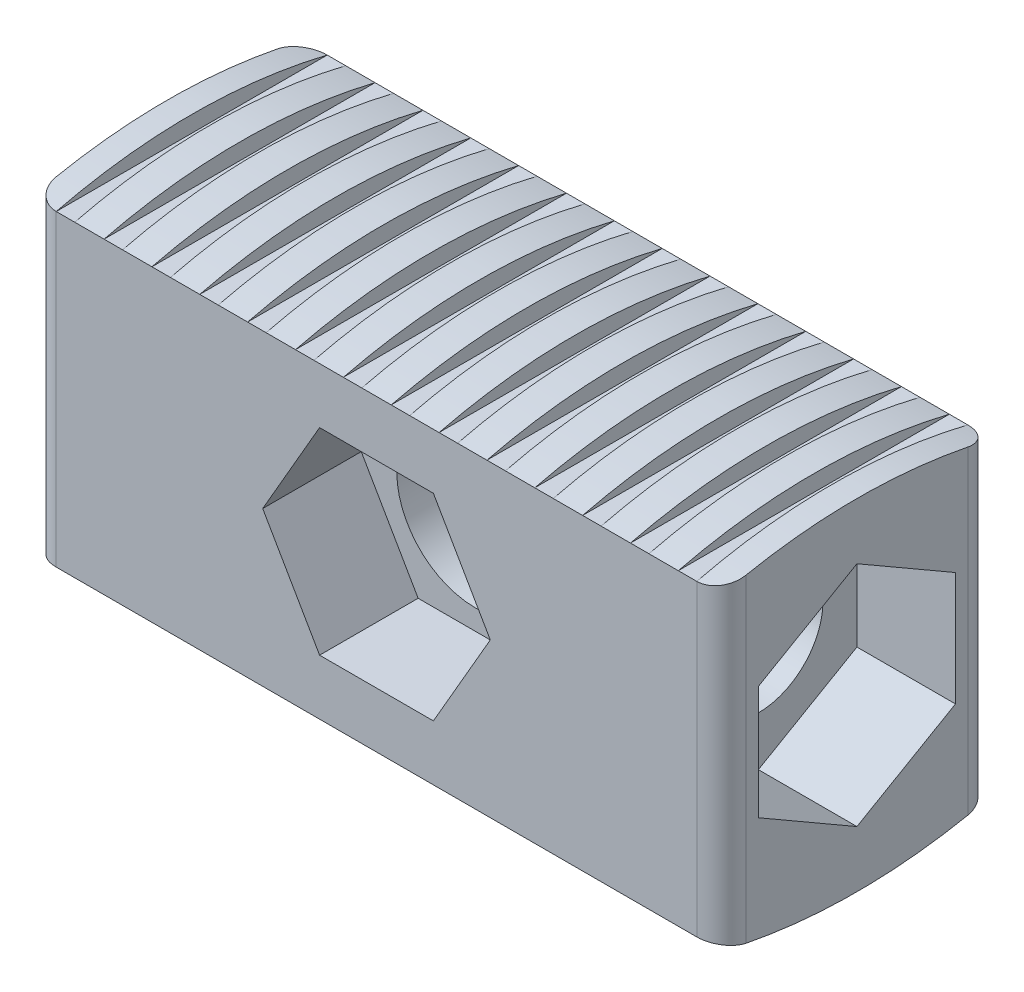
SolidWorks part; units mm, degrees
material "ABS"
ref_plane "Front Plane" through (0, 0, 0) normal (0, 0, 1) x (1, 0, 0)
ref_plane "Top Plane" through (0, 0, 0) normal (0, 1, 0) x (1, 0, 0)
ref_plane "Right Plane" through (0, 0, 0) normal (1, 0, 0) x (0, 0, -1)
sketch "Sketch1" plane through (0, 0, 0) normal (0, 0, 1) x (1, 0, 0)
  line L2 (2.8868, 5) -> (-2.8868, 5) construction
  line L3 (-2.8868, 5) -> (-5.7735, 0) construction
  line L4 (-5.7735, 0) -> (-2.8868, -5) construction
  line L5 (-2.8868, -5) -> (2.8868, -5) construction
  line L18 (0, 5) -> (0, -5) construction
  line L19 (0, 0) -> (0, -7.5) construction
  line L20 (5.7735, 0) -> (2.8868, 5) [skipped]
  line L21 (2.8868, -5) -> (5.7735, 0) [skipped]
  line L22 (-5.7735, 0) -> (-14, 0) construction
  line L23 (0, 5) -> (0, 7.5) construction
  line L24 (14, -7.5) -> (-14, -7.5)
  line L25 (-14, -7.5) -> (-14, 0)
  line L26 (-14, 0) -> (-14, 7.5)
  line L27 (-14, 7.5) -> (14, 7.5)
  line L28 (5.7735, 0) -> (14, 0) construction
  line L29 (14, 0) -> (14, 7.5)
  line L30 (14, -7.5) -> (14, 0)
  line L31 (5.7735, 0) -> (2.8868, -5) construction
  line L32 (2.8868, 5) -> (5.7735, 0) construction
  circle A0 centre (0, 0) radius 5 construction
  circle A2 centre (0, 0) radius 3.175
  dimension "D4" = 6.35
  dimension "D1" = 10
  dimension "D2" = 7.5
  dimension "D3" = 28
extrude "Boss-Extrude1" add sketch "Sketch1" along normal blind 11
sketch "Sketch3" plane through (0, 0, 11) normal (0, 0, 1) x (1, 0, 0)
  line L1 (4.6188, 0) -> (2.3094, 4)
  line L2 (2.3094, 4) -> (-2.3094, 4)
  line L3 (-2.3094, 4) -> (-4.6188, 0)
  line L4 (-4.6188, 0) -> (-2.3094, -4)
  line L5 (-2.3094, -4) -> (2.3094, -4)
  line L6 (2.3094, -4) -> (4.6188, 0)
  circle A0 centre (0, 0) radius 4 construction
  dimension "D1" = 8
extrude "Cut-Extrude3" cut sketch "Sketch3" against normal blind 4
ref_plane "Plane1" through (0, 0, 5.5) normal (0, 0, -1) x (-1, 0, 0)
sketch "Sketch6" plane through (0, -7.5, 0) normal (0, -1, 0) x (1, 0, 0)
  line L0 (-14, 11) -> (14, 11) construction
  line L1 (-13, 0) -> (-12.25, 0)
  line L2 (-13, 0) -> (-13, 11)
  line L3 (-13, 11) -> (-12.25, 11)
  line L4 (-12.25, 0) -> (-12.25, 11)
  line L5 (-14, 11) -> (-14, 0) construction
  line L6 (-11.0577, 0) -> (-11.0577, 11)
  line L7 (-11.0577, 0) -> (-10.3077, 0)
  line L8 (-10.3077, 0) -> (-10.3077, 11)
  line L9 (-11.0577, 11) -> (-10.3077, 11)
  line L10 (-9.1154, 0) -> (-9.1154, 11)
  line L11 (-9.1154, 0) -> (-8.3654, 0)
  line L12 (-8.3654, 0) -> (-8.3654, 11)
  line L13 (-9.1154, 11) -> (-8.3654, 11)
  line L14 (-7.1731, 0) -> (-7.1731, 11)
  line L15 (-7.1731, 0) -> (-6.4231, 0)
  line L16 (-6.4231, 0) -> (-6.4231, 11)
  line L17 (-7.1731, 11) -> (-6.4231, 11)
  line L18 (-5.2308, 0) -> (-5.2308, 11)
  line L19 (-5.2308, 0) -> (-4.4808, 0)
  line L20 (-4.4808, 0) -> (-4.4808, 11)
  line L21 (-5.2308, 11) -> (-4.4808, 11)
  line L22 (-3.2885, 0) -> (-3.2885, 11)
  line L23 (-3.2885, 0) -> (-2.5385, 0)
  line L24 (-2.5385, 0) -> (-2.5385, 11)
  line L25 (-3.2885, 11) -> (-2.5385, 11)
  line L26 (-1.3462, 0) -> (-1.3462, 11)
  line L27 (-1.3462, 0) -> (-0.5962, 0)
  line L28 (-0.5962, 0) -> (-0.5962, 11)
  line L29 (-1.3462, 11) -> (-0.5962, 11)
  line L30 (0.5962, 0) -> (0.5962, 11)
  line L31 (0.5962, 0) -> (1.3462, 0)
  line L32 (1.3462, 0) -> (1.3462, 11)
  line L33 (0.5962, 11) -> (1.3462, 11)
  line L34 (2.5385, 0) -> (2.5385, 11)
  line L35 (2.5385, 0) -> (3.2885, 0)
  line L36 (3.2885, 0) -> (3.2885, 11)
  line L37 (2.5385, 11) -> (3.2885, 11)
  line L38 (4.4808, 0) -> (4.4808, 11)
  line L39 (4.4808, 0) -> (5.2308, 0)
  line L40 (5.2308, 0) -> (5.2308, 11)
  line L41 (4.4808, 11) -> (5.2308, 11)
  line L42 (6.4231, 0) -> (6.4231, 11)
  line L43 (6.4231, 0) -> (7.1731, 0)
  line L44 (7.1731, 0) -> (7.1731, 11)
  line L45 (6.4231, 11) -> (7.1731, 11)
  line L46 (8.3654, 0) -> (8.3654, 11)
  line L47 (8.3654, 0) -> (9.1154, 0)
  line L48 (9.1154, 0) -> (9.1154, 11)
  line L49 (8.3654, 11) -> (9.1154, 11)
  line L50 (10.3077, 0) -> (10.3077, 11)
  line L51 (10.3077, 0) -> (11.0577, 0)
  line L52 (11.0577, 0) -> (11.0577, 11)
  line L53 (10.3077, 11) -> (11.0577, 11)
  line L54 (12.25, 0) -> (12.25, 11)
  line L55 (12.25, 0) -> (13, 0)
  line L56 (13, 0) -> (13, 11)
  line L57 (12.25, 11) -> (13, 11)
  line L62 (14, 11) -> (14, 0) construction
  dimension "D1" = 0.75
  dimension "D2" = 1
  dimension "D4" = 1
  dimension "D3" = 14
extrude "Cut-Extrude6" cut sketch "Sketch6" against normal blind 1.25
sketch "Sketch5" plane through (14, 0, 0) normal (1, 0, 0) x (0, 0, -1)
  line L0 (-11, -7.5) -> (0, -7.5) construction
  line L1 (-11, -7.5) -> (-11, 7.5) construction
  line L2 (0, -7.5) -> (0, 7.5) construction
  line L4 (-11, -6.25) -> (-11, -9.4486)
  line L5 (-11, -9.4486) -> (0, -9.4486)
  line L6 (0, -9.4486) -> (0, -6.25)
  arc A0 (-11, -6.25) -> (0, -6.25) centre (-5.5, 16.2114) ccw
  dimension "D1" = 1.25
extrude "Cut-Extrude5" cut sketch "Sketch5" against normal up to surface (28 mm away) up to face at (-14, 0, 5.5)
fillet "Fillet2" radius 1 4 edges at (14, 0.625, 0) (14, 0.625, 11) (-14, 0.625, 0) (-14, 0.625, 11)
mirror "Mirror3" about plane through (0, 0, 5.5) normal (0, 0, -1) of "Cut-Extrude3"
sketch "Sketch8" plane through (-14, 0, 0) normal (-1, 0, 0) x (0, 0, 1)
  line L0 (5.5, 0) -> (5.5, -9.7057) construction
  line L2 (0, 0) -> (5.5, 0) construction
  circle A0 centre (5.5, 0) radius 2.625
  dimension "D1" = 5.25
extrude "Cut-Extrude8" cut sketch "Sketch8" against normal blind 6
sketch "Sketch9" plane through (-14, 0, 0) normal (-1, 0, 0) x (0, 0, 1)
  line L1 (9.5, -2.3094) -> (9.5, 2.3094)
  line L2 (9.5, 2.3094) -> (5.5, 4.6188)
  line L3 (5.5, 4.6188) -> (1.5, 2.3094)
  line L4 (1.5, 2.3094) -> (1.5, -2.3094)
  line L5 (1.5, -2.3094) -> (5.5, -4.6188)
  line L6 (5.5, -4.6188) -> (9.5, -2.3094)
  circle A0 centre (5.5, 0) radius 4 construction
  point P1 (9.5, 0)
  dimension "D1" = 8
extrude "Cut-Extrude9" cut sketch "Sketch9" against normal blind 4
mirror "Mirror4" about plane through (0, 0, 0) normal (1, 0, 0) of "Cut-Extrude9", "Cut-Extrude8"
mirror "Mirror5" about plane through (0, 0, 0) normal (0, 1, 0) of "Cut-Extrude5", "Cut-Extrude6"
